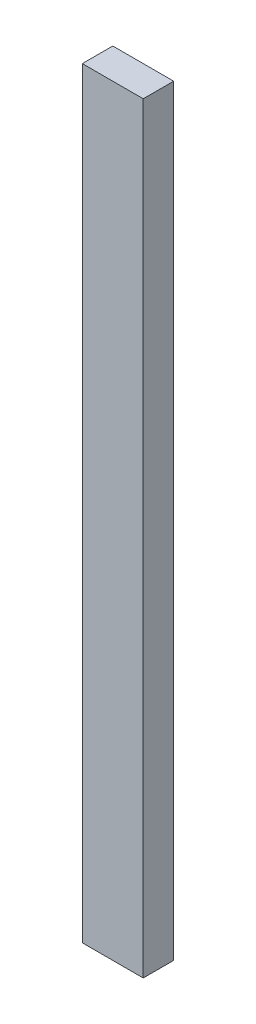
SolidWorks part; units mm, degrees
material "Stainless Steel (ferritic)"
ref_plane "Front Plane" through (0, 0, 0) normal (0, 0, 1) x (1, 0, 0)
ref_plane "Top Plane" through (0, 0, 0) normal (0, 1, 0) x (1, 0, 0)
ref_plane "Right Plane" through (0, 0, 0) normal (1, 0, 0) x (0, 0, -1)
sketch "Sketch1" plane through (0, 0, 0) normal (0, 0, 1) x (1, 0, 0)
  line L1 (-20, -250) -> (20, -250)
  line L2 (-20, -250) -> (-20, 250)
  line L3 (-20, 250) -> (20, 250)
  line L4 (20, -250) -> (20, 250)
  line L5 (-20, -250) -> (20, 250) construction
  line L6 (-20, 250) -> (20, -250) construction
  point P0 (0, 0)
  dimension "D1" = 40
  dimension "D2" = 500
extrude "Boss-Extrude1" add sketch "Sketch1" along normal blind 20
sketch "Sketch2" plane through (0, 0, 20) normal (0, 0, 1) x (1, 0, 0)
  line L0 (0, 250) -> (20, 250) construction
  line L1 (20, 250) -> (-20, 250) construction
  line L2 (10, 250) -> (10, -250) construction
  line L3 (-20, -250) -> (20, -250) construction
  line L4 (20, -250) -> (20, 250) construction
  point P8 (10, 200)
  point P9 (10, -200)
  point P10 (10, 100)
  point P11 (10, -100)
  point P12 (10, 0)
  dimension "D1" = 200
  dimension "D2" = 100
  dimension "D3" = 200
  dimension "D4" = 100
  dimension "D5" = 10
